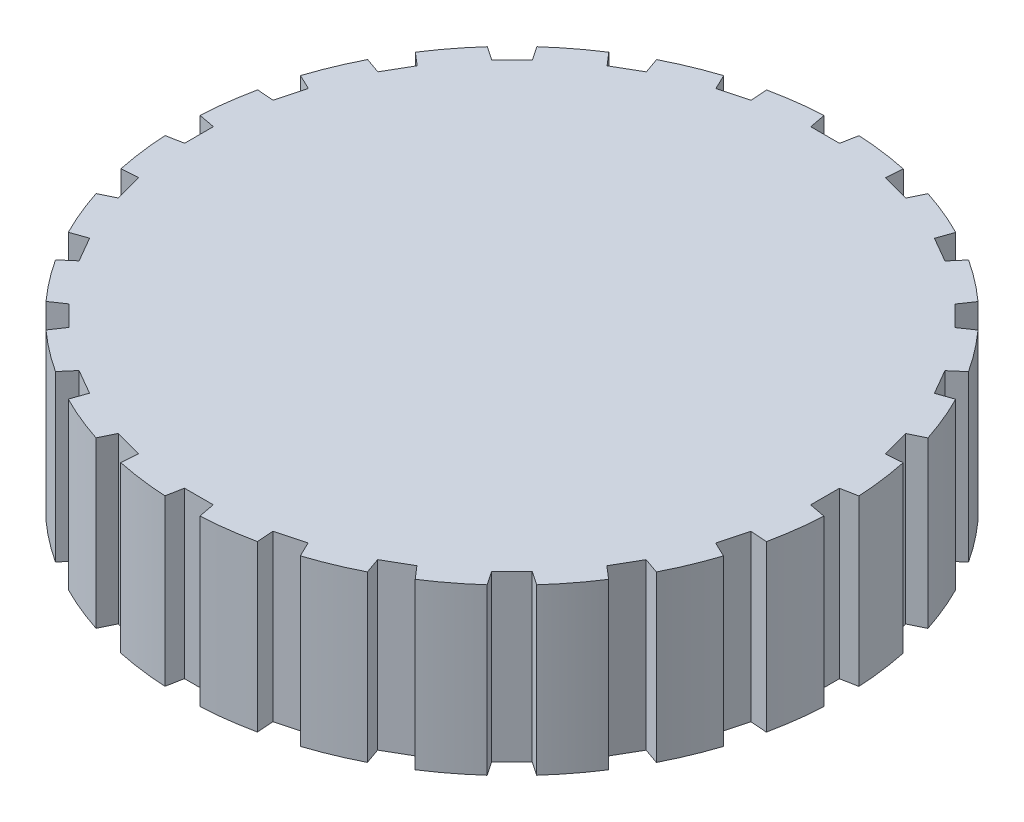
SolidWorks part; units mm, degrees
ref_plane "Front Plane" through (0, 0, 0) normal (0, 0, 1) x (1, 0, 0)
ref_plane "Top Plane" through (0, 0, 0) normal (0, 1, 0) x (1, 0, 0)
ref_plane "Right Plane" through (0, 0, 0) normal (1, 0, 0) x (0, 0, -1)
sketch "Sketch5" plane through (0, 0, 0) normal (0, 1, 0) x (1, 0, 0)
  circle A0 centre (0, 0) radius 38.1
extrude "Boss-Extrude2" add sketch "Sketch5" along normal blind 19.05
sketch "Sketch8" plane through (0, 19.05, 0) normal (0, 1, 0) x (1, 0, 0)
  line L0 (0, 38.1) -> (2.0388, 38.1)
  line L1 (0, 38.1) -> (-2.021, 38.1)
  line L5 (0.0089, 36.15) -> (-1.6511, 36.15)
  line L6 (0.0089, 36.15) -> (1.6689, 36.15)
  line L7 (-2.021, 38.1) -> (-1.6511, 36.15)
  line L8 (2.0388, 38.1) -> (1.6689, 36.15)
  point P0 (0, 38.1)
  point P2 (0, 38.1)
  point P3 (0, 0)
  point P4 (0, 0)
  point P9 (0, 0)
  dimension "D1" = 1.66
  dimension "D2" = 1.66
  dimension "D3" = 1.95
extrude "Cut-Extrude1" cut sketch "Sketch8" against normal blind 22.05
pattern_circular "CirPattern1" count 24 over 360 about axis through (0, 19.05, 0) along (0, 1, 0) of "Cut-Extrude1"
sketch "Sketch9" plane through (0, 19.05, 0) normal (0, 1, 0) x (1, 0, 0)
  line L0 (0, 7.25) -> (2.6, 7.25)
  line L1 (0, 7.25) -> (-2.6, 7.25)
  line L2 (-2.6, 7.25) -> (-2.6, 6.7678)
  line L3 (2.6, 7.25) -> (2.6, 6.7678)
  line L4 (-2.6, 7.25) -> (-2.6, 9.75)
  line L5 (-2.6, 9.75) -> (2.6, 9.75)
  line L6 (2.6, 9.75) -> (2.6, 7.25)
  circle A0 centre (0, 0) radius 7.25
extrude "Cut-Extrude2" [suppressed] cut sketch "Sketch9" against normal blind 25.4 contours A0 | L6 L5 L4 L1 L0 | A0 L1 L2 | A0 L3 L0
